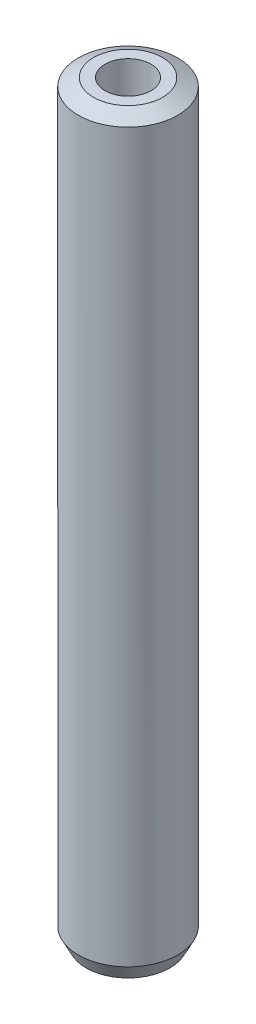
SolidWorks part; units mm, degrees
ref_plane "Front Plane" through (0, 0, 0) normal (0, 0, 1) x (1, 0, 0)
ref_plane "Top Plane" through (0, 0, 0) normal (0, 1, 0) x (1, 0, 0)
ref_plane "Right Plane" through (0, 0, 0) normal (1, 0, 0) x (0, 0, -1)
sketch "Sketch1" plane through (0, 0, 0) normal (0, 1, 0) x (1, 0, 0)
  circle A0 centre (0, 0) radius 25
  dimension "SHAFT_OD" = 50
extrude "Boss-Extrude1" add sketch "Sketch1" along normal blind 377.0818
sketch "Sketch2" plane through (0, 0, 0) normal (0, 1, 0) x (1, 0, 0)
  circle A0 centre (0, 0) radius 11.5721
  dimension "BORE_D" = 23.1443
extrude "Cut-Extrude1" cut sketch "Sketch2" along normal through all
chamfer "Chamfer1" distance 3.9691 angle 62.617 2 edges at (0, 377.0818, 25) (0, 0, 25) first distance on face at (0, 377.0818, 25) first distance on face at (0, 0, 11.5721)
